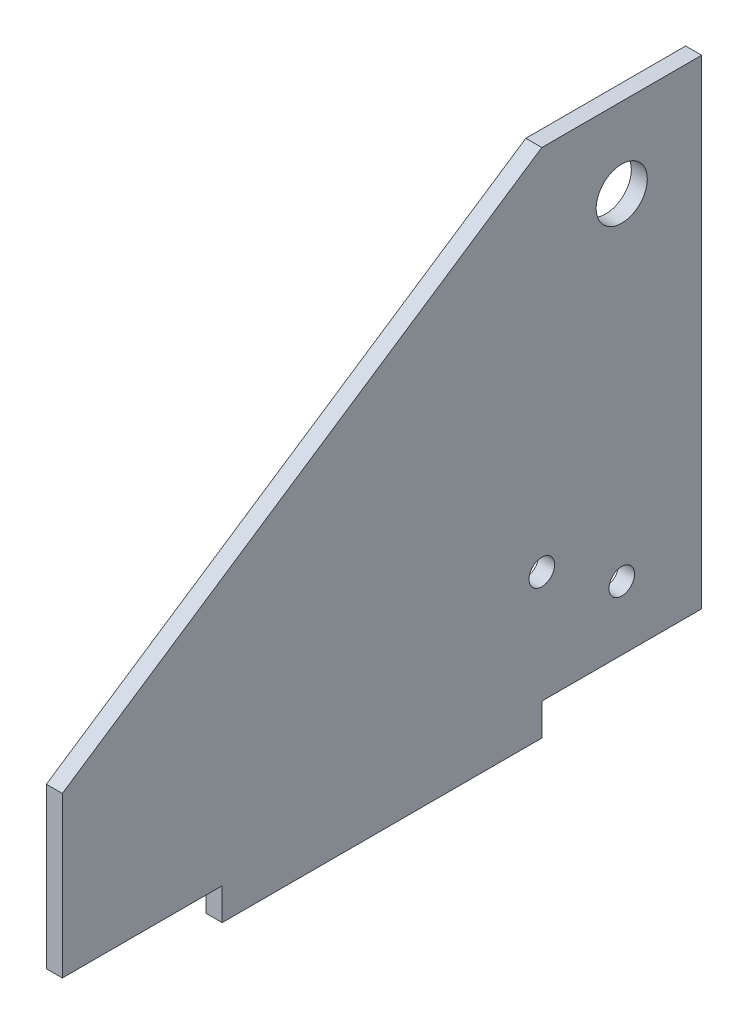
SolidWorks part; units mm, degrees
ref_plane "Alzado" through (0, 0, 0) normal (0, 0, 1) x (1, 0, 0)
ref_plane "Planta" through (0, 0, 0) normal (0, 1, 0) x (1, 0, 0)
ref_plane "Vista lateral" through (0, 0, 0) normal (1, 0, 0) x (0, 0, -1)
sketch "Croquis1" plane through (0, 0, 0) normal (1, 0, 0) x (0, 0, -1)
  line L0 (50, 75) -> (-100, -25)
  line L1 (-100, -75) -> (-50, -75)
  line L2 (-100, -75) -> (-100, -25)
  line L3 (50, 75) -> (100, 75)
  line L4 (100, -75) -> (100, 75)
  line L5 (100, 0) -> (-62.5, 0) construction
  line L6 (75, 75) -> (75, -75) construction
  line L7 (0, 41.6667) -> (0, -85) construction
  line L9 (-50, -75) -> (-50, -85)
  line L10 (-50, -85) -> (50, -85)
  line L11 (50, -75) -> (50, -85)
  line L14 (50, -75) -> (100, -75)
  circle A0 centre (75, 50) radius 8
  circle A1 centre (75, -55) radius 4
  circle A2 centre (50, -40) radius 4
  point P0 (0, 0)
  point P13 (0, -75)
  dimension "D6" = 16
  dimension "D10" = 8
  dimension "D12" = 8
  dimension "D1" = 150
  dimension "D2" = 200
  dimension "D3" = 50
  dimension "D4" = 50
  dimension "D5" = 50
  dimension "D7" = 100
  dimension "D8" = 50
  dimension "D9" = 10
  dimension "D11" = 20
  dimension "D13" = 25
  dimension "D14" = 15
extrude "Saliente-Extruir1" add sketch "Croquis1" along normal blind 5
